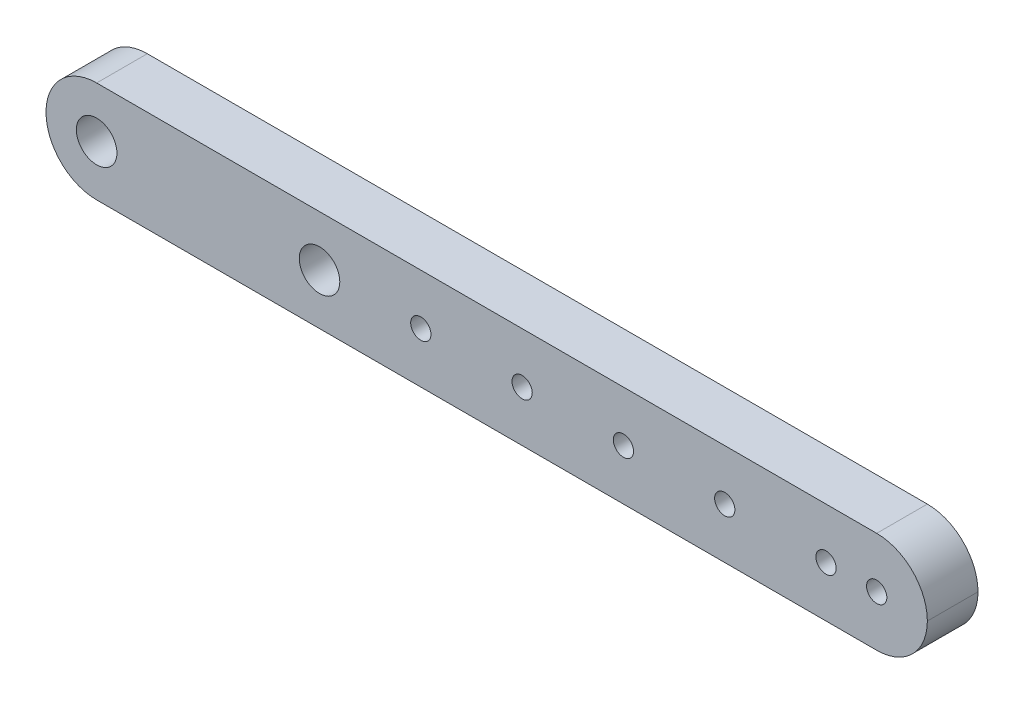
SolidWorks part; units mm, degrees
material "AISI 316 Barre d'acier inoxydable recuit (SS)"
ref_plane "Plan de face" through (0, 0, 0) normal (0, 0, 1) x (1, 0, 0)
ref_plane "Plan de dessus" through (0, 0, 0) normal (0, 1, 0) x (1, 0, 0)
ref_plane "Plan de droite" through (0, 0, 0) normal (1, 0, 0) x (0, 0, -1)
sketch "Esquisse1" plane through (0, 0, 0) normal (0, 0, 1) x (1, 0, 0)
  line L0 (0, 10) -> (174, 10) construction
  line L1 (0, 20) -> (174, 20) construction
  line L2 (0, 20) -> (0, 0)
  line L3 (0, 0) -> (174, 0) construction
  line L4 (174, 20) -> (174, 0)
  line L5 (87, 20) -> (87, 0) construction
  line L6 (0, 20) -> (60, 20)
  line L7 (174, 20) -> (154, 20)
  line L8 (60, 20) -> (154, 20)
  line L10 (174, 0) -> (154, 0)
  line L11 (0, 0) -> (60, 0)
  line L13 (154, 0) -> (60, 0)
  circle A0 centre (10, 10) radius 4
  circle A1 centre (54, 10) radius 4
  circle A2 centre (154, 10) radius 2
  circle A3 centre (164, 10) radius 2
  circle A4 centre (74, 10) radius 2
  circle A36 centre (94, 10) radius 2
  circle A37 centre (114, 10) radius 2
  circle A38 centre (134, 10) radius 2
  dimension "D3" = 8
  dimension "D4" = 44
  dimension "D7" = 4
  dimension "D9" = 20
  dimension "D10" = 4
  dimension "D11" = 4
  dimension "D12" = 20
  dimension "D13" = 60
  dimension "D14" = 20
  dimension "D1" = 20
  dimension "D2" = 174
  dimension "D5" = 10
  dimension "D6" = 10
  dimension "D8" = 10
extrude "Boss.-Extru.1" add sketch "Esquisse1" along normal blind 10
fillet "Congé1" radius 10 4 edges at (0, 0, 5) (0, 20, 5) (174, 0, 5) (174, 20, 5)
